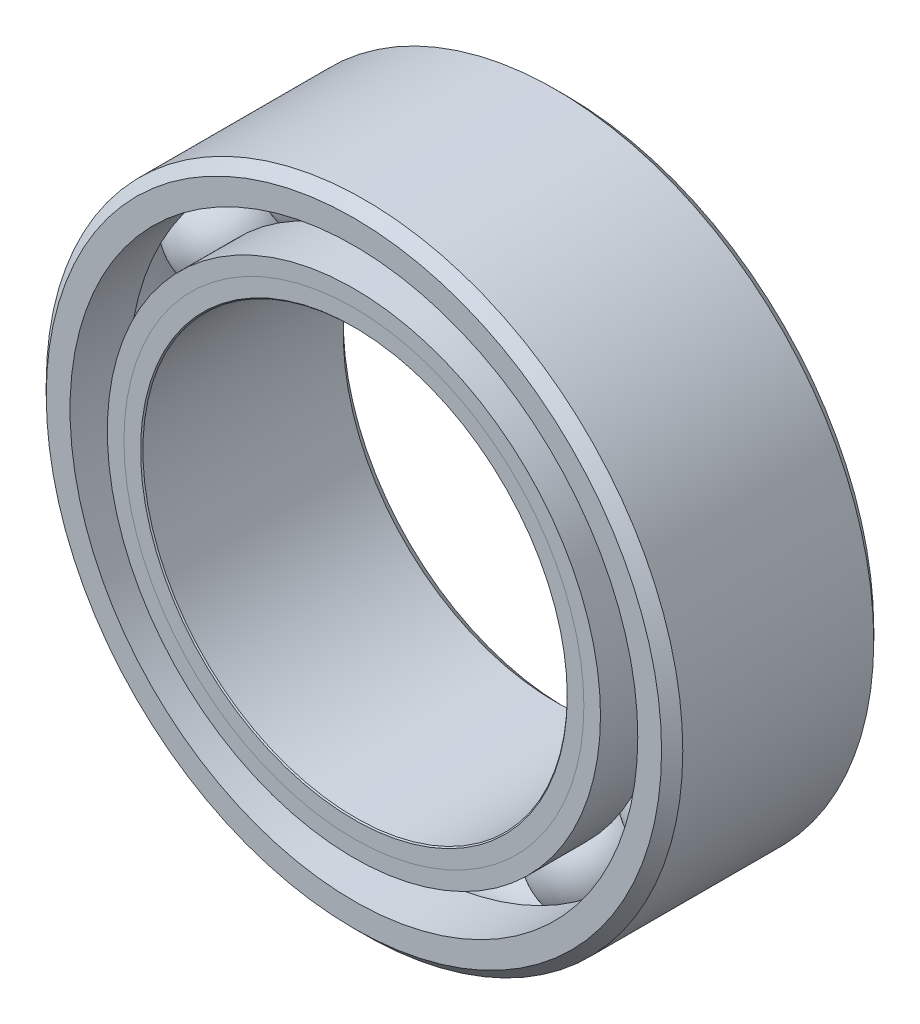
SolidWorks part; units mm, degrees
ref_plane "Front Plane" through (0, 0, 0) normal (0, 0, 1) x (1, 0, 0)
ref_plane "Top Plane" through (0, 0, 0) normal (0, 1, 0) x (1, 0, 0)
ref_plane "Right Plane" through (0, 0, 0) normal (1, 0, 0) x (0, 0, -1)
sketch "Sketch1" plane through (0, 0, 0) normal (1, 0, 0) x (0, 0, -1)
  line L0 (-1.5875, 0) -> (1.5875, 0) construction
  line L1 (0, 4.7625) -> (0, -4.7625) construction
  line L2 (1.4288, 4.7625) -> (-1.4288, 4.7625)
  line L3 (-1.4288, 4.7625) -> (-1.5875, 4.6037)
  line L4 (-1.5875, 4.6037) -> (-1.5875, 4.2479)
  line L5 (-1.5875, 4.2479) -> (-0.7056, 4.2479)
  line L6 (1.5875, 4.2479) -> (0.7056, 4.2479)
  line L7 (1.5875, 4.6037) -> (1.5875, 4.2479)
  line L8 (1.4288, 4.7625) -> (1.5875, 4.6037)
  line L9 (0, 4.7625) -> (0, 3.9688) construction
  line L10 (0, 3.9688) -> (0, 3.175) construction
  arc A0 (-0.7056, 4.2479) -> (0.7056, 4.2479) centre (0, 3.9688) cw
  point P14 (0, 3.175)
  dimension "Width" = 3.175
  dimension "OD" = 9.525
  dimension "D1" = 45
  dimension "D2" = 0.1588
  dimension "D3" = 1.4111
  dimension "D4" = 0.2791
revolve "Revolve1" add sketch "Sketch1" angle 360 about L0
sketch "Sketch2" plane through (0, 0, 0) normal (1, 0, 0) x (0, 0, -1)
  line L0 (-1.5875, 3.6896) -> (-0.7056, 3.6896)
  line L1 (-1.5875, 4.6037) -> (-1.5875, -4.6037) construction
  line L2 (-1.5875, 3.6896) -> (-1.5875, 3.4411)
  line L3 (-1.5875, 3.4411) -> (-1.3389, 3.1925)
  line L4 (-1.3389, 3.1925) -> (0, 3.1925)
  line L5 (0, 4.7625) -> (0, -4.7625) construction
  line L6 (0, 3.1925) -> (0, 3.21)
  line L7 (0, 3.21) -> (0, 3.175) construction
  line L8 (-1.5875, 3.6896) -> (-1.5875, 3.1925) construction
  line L9 (-1.5875, 3.1925) -> (-1.3389, 3.1925) construction
  arc A0 (-0.7056, 3.6896) -> (0, 3.21) centre (0, 3.9688) ccw
  arc A1 (0.7056, 4.2479) -> (-0.7056, 4.2479) centre (0, 3.9688) ccw construction
  circle A2 centre (0, 3.9688) radius 0.7588 construction
  dimension "D1" = 45
revolve "Revolve2" add sketch "Sketch2" angle 360 about L0
sketch "Sketch3" plane through (0, 0, 0) normal (1, 0, 0) x (0, 0, -1)
  line L0 (-1.5875, 3.4411) -> (-1.3389, 3.1925)
  line L1 (-1.3389, 3.1925) -> (0, 3.1925)
  line L2 (0, 3.1925) -> (0, 3.21)
  line L3 (-1.5875, 3.4411) -> (-1.5875, 3.1925)
  line L4 (-1.5875, 3.6896) -> (-1.5875, 3.1925) construction
  line L5 (-1.5875, 3.1925) -> (-1.57, 3.175)
  line L6 (-1.57, 3.175) -> (1.4288, 3.175)
  line L7 (1.4288, 4.7625) -> (1.4288, -4.7625) construction
  line L8 (1.4288, 3.175) -> (1.5875, 3.3337)
  line L9 (1.5875, -4.6037) -> (1.5875, 4.6037) construction
  line L10 (1.5875, 3.3337) -> (1.5875, 3.6896)
  line L11 (1.5875, 3.6896) -> (0.7056, 3.6896)
  line L13 (1.4288, 4.7625) -> (1.5875, 4.6037) construction
  circle A0 centre (0, 3.9688) radius 0.7588 construction
  arc A1 (0.7056, 3.6896) -> (0, 3.21) centre (0, 3.9688) cw
revolve "Revolve3" add sketch "Sketch3" angle 360 about L0
sketch "Sketch4" plane through (0, 0, 0) normal (1, 0, 0) x (0, 0, -1)
  line L0 (-0.7588, 3.9688) -> (0.7588, 3.9688)
  circle A1 centre (0, 3.9688) radius 0.7588 construction
  arc A2 (-0.7588, 3.9688) -> (0.7588, 3.9688) centre (0, 3.9688) cw
  arc A3 (0.7056, 4.2479) -> (-0.7056, 4.2479) centre (0, 3.9688) ccw construction
revolve "Revolve4" add sketch "Sketch4" angle 360 about L0
ref_axis "Axis1" through (0, 0, -1.5875) along (0, 0, 1)
pattern_circular "CirPattern1" count 12 every 30 about axis through (0, 0, -1.5875) along (0, 0, 1) of bodies 104
equation "\"D2@Sketch1\" = \"Width@Sketch1\"*.05"
equation "\"D3@Sketch1\" = \"Width@Sketch1\"/2.25"
equation "\"D4@Sketch1\" = (((\"OD@Sketch1\"-\"Width@Sketch1\")/2)/3.25)/3.5"
equation "\"D2@CirPattern1\" = 360/\"Balls@CirPattern1\""
